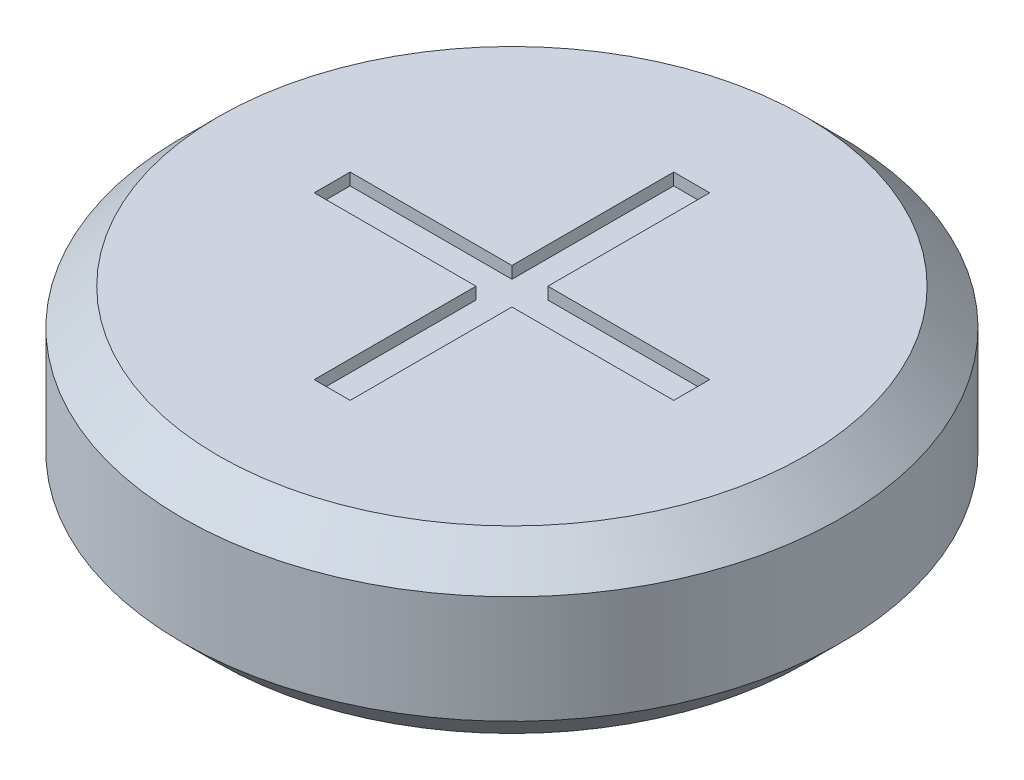
SolidWorks part; units mm, degrees
ref_plane "Front Plane" through (0, 0, 0) normal (0, 0, 1) x (1, 0, 0)
ref_plane "Top Plane" through (0, 0, 0) normal (0, 1, 0) x (1, 0, 0)
ref_plane "Right Plane" through (0, 0, 0) normal (1, 0, 0) x (0, 0, -1)
sketch "Sketch1" plane through (0, 0, 0) normal (0, 1, 0) x (1, 0, 0)
  circle A0 centre (0, 0) radius 27.5
  dimension "D1" = 55
extrude "Boss-Extrude1" add sketch "Sketch1" along normal blind 15
chamfer "Chamfer1" distance 3 angle 45 2 edges at (0, 0, 27.5) (0, 15, 27.5)
sketch "Sketch2" plane through (0, 15, 0) normal (0, 1, 0) x (1, 0, 0)
  line L0 (-24.5, 0) -> (24.5, 0) construction
  line L1 (0, 24.5) -> (0, -24.5) construction
  line L2 (-1.5, 15) -> (1.5, 15)
  line L3 (-15, -1.5) -> (-15, 1.5)
  line L4 (15, 1.5) -> (15, -1.5)
  line L5 (-1.5, -15) -> (1.5, -15)
  line L6 (-15, 1.5) -> (-1.5, 1.5)
  line L7 (-1.5, 1.5) -> (-1.5, 15)
  line L8 (1.5, 15) -> (1.5, 1.5)
  line L9 (1.5, 1.5) -> (15, 1.5)
  line L10 (15, -1.5) -> (1.5, -1.5)
  line L11 (1.5, -1.5) -> (1.5, -15)
  line L12 (-1.5, -15) -> (-1.5, -1.5)
  line L13 (-1.5, -1.5) -> (-15, -1.5)
  circle A0 centre (0, 0) radius 24.5 construction
  point P7 (0, 0)
  point P10 (0, 0)
  point P13 (0, 15)
  point P16 (-15, 0)
  point P19 (15, 0)
  point P22 (0, -15)
  dimension "D1" = 30
  dimension "D2" = 3
extrude "Cut-Extrude1" cut sketch "Sketch2" against normal blind 1
sketch "Sketch3" plane through (0, 0, 0) normal (0, -1, 0) x (1, 0, 0)
  line L1 (-15, 1.5) -> (15, 1.5)
  line L2 (-15, 1.5) -> (-15, -1.5)
  line L3 (-15, -1.5) -> (15, -1.5)
  line L4 (15, 1.5) -> (15, -1.5)
  line L5 (0, -1.5) -> (0, 1.5) construction
  line L6 (-15, 0) -> (15, 0) construction
  point P0 (0, 0)
  dimension "D1" = 30
  dimension "D2" = 3
extrude "Cut-Extrude2" cut sketch "Sketch3" against normal blind 1
